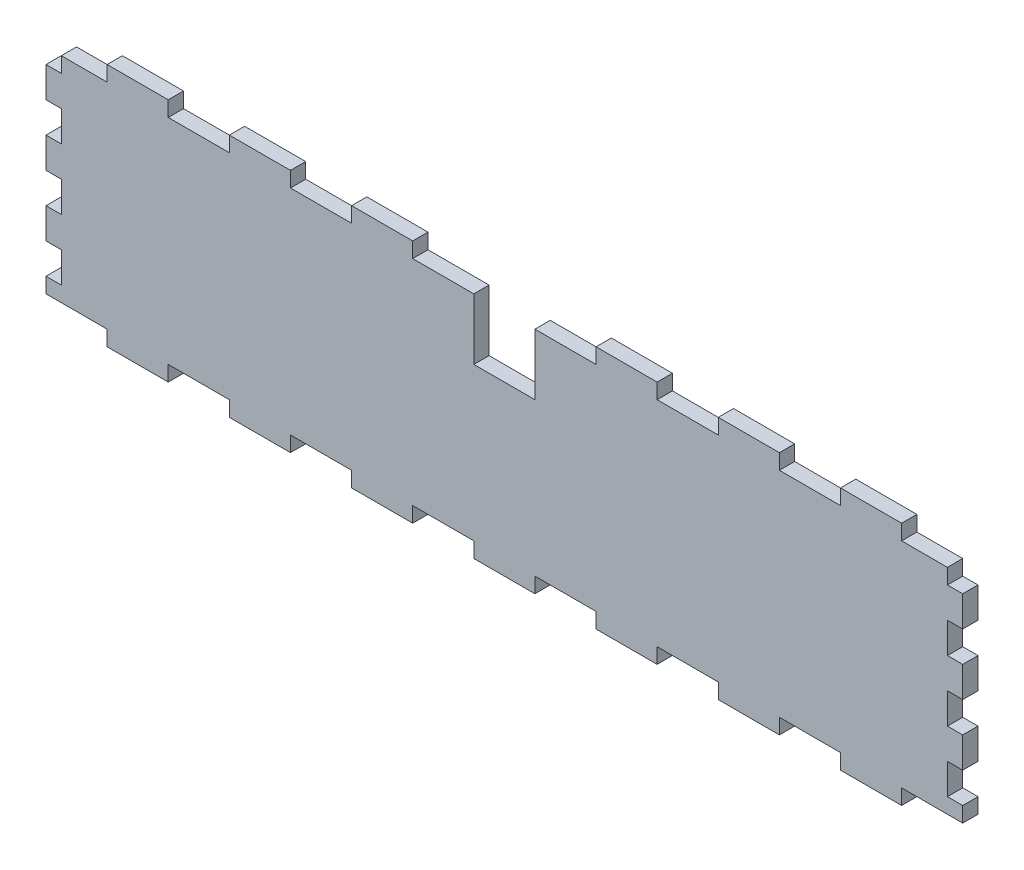
SolidWorks part; units mm, degrees
ref_plane "Front Plane" through (0, 0, 0) normal (0, 0, 1) x (1, 0, 0)
ref_plane "Top Plane" through (0, 0, 0) normal (0, 1, 0) x (1, 0, 0)
ref_plane "Right Plane" through (0, 0, 0) normal (1, 0, 0) x (0, 0, -1)
sketch "Sketch1" plane through (0, 0, 0) normal (0, 0, 1) x (1, 0, 0)
  line L1 (-190.5, -50.8) -> (190.5, -50.8)
  line L2 (-190.5, -50.8) -> (-190.5, 50.8)
  line L3 (-190.5, 50.8) -> (190.5, 50.8)
  line L4 (190.5, -50.8) -> (190.5, 50.8)
  line L5 (-190.5, -50.8) -> (190.5, 50.8) construction
  line L6 (-190.5, 50.8) -> (190.5, -50.8) construction
  point P0 (0, 0)
  dimension "D1" = 381
  dimension "D2" = 101.6
extrude "Boss-Extrude1" add sketch "Sketch1" along normal blind 6.35
sketch "Sketch2" plane through (0, 0, 6.35) normal (0, 0, 1) x (1, 0, 0)
  line L0 (-139.7, 50.8) -> (-139.7, 44.45)
  line L1 (-190.5, 50.8) -> (-165.1, 50.8)
  line L2 (-190.5, 50.8) -> (-190.5, 44.45)
  line L3 (-190.5, 44.45) -> (-165.1, 44.45)
  line L4 (-165.1, 50.8) -> (-165.1, 44.45)
  line L5 (-139.7, 50.8) -> (-114.3, 50.8)
  line L6 (-114.3, 50.8) -> (-114.3, 44.45)
  line L7 (-139.7, 44.45) -> (-114.3, 44.45)
  line L8 (-88.9, 50.8) -> (-88.9, 44.45)
  line L9 (-88.9, 50.8) -> (-63.5, 50.8)
  line L10 (-63.5, 50.8) -> (-63.5, 44.45)
  line L11 (-88.9, 44.45) -> (-63.5, 44.45)
  line L12 (-38.1, 50.8) -> (-38.1, 44.45)
  line L13 (-38.1, 50.8) -> (-12.7, 50.8)
  line L14 (-12.7, 50.8) -> (-12.7, 44.45)
  line L15 (-38.1, 44.45) -> (-12.7, 44.45)
  line L16 (12.7, 50.8) -> (12.7, 44.45)
  line L17 (12.7, 50.8) -> (38.1, 50.8)
  line L18 (38.1, 50.8) -> (38.1, 44.45)
  line L19 (12.7, 44.45) -> (38.1, 44.45)
  line L20 (63.5, 50.8) -> (63.5, 44.45)
  line L21 (63.5, 50.8) -> (88.9, 50.8)
  line L22 (88.9, 50.8) -> (88.9, 44.45)
  line L23 (63.5, 44.45) -> (88.9, 44.45)
  line L24 (114.3, 50.8) -> (114.3, 44.45)
  line L25 (114.3, 50.8) -> (139.7, 50.8)
  line L26 (139.7, 50.8) -> (139.7, 44.45)
  line L27 (114.3, 44.45) -> (139.7, 44.45)
  line L28 (165.1, 50.8) -> (165.1, 44.45)
  line L29 (165.1, 50.8) -> (190.5, 50.8)
  line L30 (190.5, 50.8) -> (190.5, 44.45)
  line L31 (165.1, 44.45) -> (190.5, 44.45)
  line L32 (0, 0) -> (17.1366, 0)
  line L33 (0, 0) -> (0, 20.0911)
  line L34 (165.1, -50.8) -> (190.5, -50.8)
  line L35 (190.5, -50.8) -> (190.5, -44.45)
  line L36 (165.1, -44.45) -> (190.5, -44.45)
  line L37 (165.1, -50.8) -> (165.1, -44.45)
  line L38 (114.3, -50.8) -> (139.7, -50.8)
  line L39 (139.7, -50.8) -> (139.7, -44.45)
  line L40 (114.3, -44.45) -> (139.7, -44.45)
  line L41 (114.3, -50.8) -> (114.3, -44.45)
  line L42 (63.5, -50.8) -> (88.9, -50.8)
  line L43 (88.9, -50.8) -> (88.9, -44.45)
  line L44 (63.5, -44.45) -> (88.9, -44.45)
  line L45 (63.5, -50.8) -> (63.5, -44.45)
  line L46 (12.7, -50.8) -> (38.1, -50.8)
  line L47 (38.1, -50.8) -> (38.1, -44.45)
  line L48 (12.7, -44.45) -> (38.1, -44.45)
  line L49 (12.7, -50.8) -> (12.7, -44.45)
  line L50 (-38.1, -50.8) -> (-12.7, -50.8)
  line L51 (-12.7, -50.8) -> (-12.7, -44.45)
  line L52 (-38.1, -44.45) -> (-12.7, -44.45)
  line L53 (-38.1, -50.8) -> (-38.1, -44.45)
  line L54 (-88.9, -50.8) -> (-63.5, -50.8)
  line L55 (-63.5, -50.8) -> (-63.5, -44.45)
  line L56 (-88.9, -44.45) -> (-63.5, -44.45)
  line L57 (-88.9, -50.8) -> (-88.9, -44.45)
  line L58 (-139.7, -50.8) -> (-114.3, -50.8)
  line L59 (-114.3, -50.8) -> (-114.3, -44.45)
  line L60 (-139.7, -44.45) -> (-114.3, -44.45)
  line L61 (-139.7, -50.8) -> (-139.7, -44.45)
  line L62 (-190.5, -44.45) -> (-165.1, -44.45)
  line L63 (-165.1, -50.8) -> (-165.1, -44.45)
  line L64 (-190.5, -50.8) -> (-165.1, -50.8)
  line L65 (-190.5, -50.8) -> (-190.5, -44.45)
  line L66 (-190.5, 25.4) -> (-190.5, 12.7)
  line L67 (-190.5, 50.8) -> (-184.15, 50.8)
  line L68 (-190.5, 50.8) -> (-190.5, 38.1)
  line L69 (-190.5, 38.1) -> (-184.15, 38.1)
  line L70 (-184.15, 50.8) -> (-184.15, 38.1)
  line L71 (-190.5, 25.4) -> (-184.15, 25.4)
  line L72 (-184.15, 25.4) -> (-184.15, 12.7)
  line L73 (-190.5, 12.7) -> (-184.15, 12.7)
  line L74 (-190.5, 0) -> (-190.5, -12.7)
  line L75 (-190.5, 0) -> (-184.15, 0)
  line L76 (-184.15, 0) -> (-184.15, -12.7)
  line L77 (-190.5, -12.7) -> (-184.15, -12.7)
  line L78 (-190.5, -25.4) -> (-190.5, -38.1)
  line L79 (-190.5, -25.4) -> (-184.15, -25.4)
  line L80 (-184.15, -25.4) -> (-184.15, -38.1)
  line L81 (-190.5, -38.1) -> (-184.15, -38.1)
  line L83 (190.5, -25.4) -> (184.15, -25.4)
  line L84 (184.15, -25.4) -> (184.15, -38.1)
  line L85 (190.5, -38.1) -> (184.15, -38.1)
  line L86 (190.5, -25.4) -> (190.5, -38.1)
  line L87 (190.5, 0) -> (184.15, 0)
  line L88 (184.15, 0) -> (184.15, -12.7)
  line L89 (190.5, -12.7) -> (184.15, -12.7)
  line L90 (190.5, 0) -> (190.5, -12.7)
  line L91 (190.5, 25.4) -> (184.15, 25.4)
  line L92 (184.15, 25.4) -> (184.15, 12.7)
  line L93 (190.5, 12.7) -> (184.15, 12.7)
  line L94 (190.5, 25.4) -> (190.5, 12.7)
  line L95 (190.5, 38.1) -> (184.15, 38.1)
  line L96 (184.15, 50.8) -> (184.15, 38.1)
  line L97 (190.5, 50.8) -> (184.15, 50.8)
  line L98 (190.5, 50.8) -> (190.5, 38.1)
  line M51 (190.5, -50.8) -> (190.5, 50.8)
  line M52 (190.5, 50.8) -> (-190.5, 50.8)
  line M53 (-190.5, 50.8) -> (-190.5, -50.8)
  line M54 (-190.5, -50.8) -> (190.5, -50.8)
  dimension "D1" = 25.4
  dimension "D2" = 6.35
  dimension "D4" = 6.35
  dimension "D5" = 12.7
  dimension "D3" = 8
  dimension "D6" = 4
extrude "Cut-Extrude1" cut sketch "Sketch2" against normal blind 6.35 contours L70 L3 L4 M52 | L70 L1 L3 M53 | L70 L3 L69 M53 | L73 L72 L71 M53 | L77 L76 L75 M53 | L81 L80 L79 M53 | L63 L62 M54 M53 | L61 L59 L60 M54 | L57 L55 L56 M54 | L53 L51 L52 M54 | L49 L47 L48 M54 | L0 L7 L6 M52 | L8 L11 L10 M52 | L12 L15 L14 M52 | L16 L19 L18 M52 | L20 L23 L22 M52 | L45 L43 L44 M54 | L41 L39 L40 M54 | L24 L27 L26 M52 | L96 L29 L28 L31 | L96 L31 M52 M51 | L31 L96 L95 M51 | L93 L91 L92 M51 | L89 L87 L88 M51 | L85 L83 L84 M51 | L37 L36 M54 M51 region at (-127, 47.625, 6.35) region at (-174.625, 47.625, 6.35) region at (-76.2, 47.625, 6.35) region at (-187.325, 47.625, 6.35) region at (-187.325, 41.275, 6.35) region at (-25.4, 47.625, 6.35) region at (25.4, 47.625, 6.35) region at (-187.325, 19.05, 6.35) region at (76.2, 47.625, 6.35) region at (-187.325, -6.35, 6.35) region at (127, 47.625, 6.35) region at (-187.325, -31.75, 6.35) region at (174.625, 47.625, 6.35) region at (-177.8, -47.625, 6.35) region at (187.325, 47.625, 6.35) region at (187.325, 41.275, 6.35) region at (-127, -47.625, 6.35) region at (187.325, 19.05, 6.35) region at (-76.2, -47.625, 6.35) region at (187.325, -6.35, 6.35) region at (-25.4, -47.625, 6.35) region at (187.325, -31.75, 6.35) region at (25.4, -47.625, 6.35) region at (177.8, -47.625, 6.35) region at (76.2, -47.625, 6.35) region at (127, -47.625, 6.35)
sketch "Sketch3" plane through (0, 0, 6.35) normal (0, 0, 1) x (1, 0, 0)
  line L0 (12.7, 50.8) -> (12.7, 44.45) construction
  line L1 (-12.7, 50.8) -> (12.7, 50.8)
  line L2 (-12.7, 50.8) -> (-12.7, 19.05)
  line L3 (-12.7, 19.05) -> (12.7, 19.05)
  line L4 (12.7, 50.8) -> (12.7, 19.05)
  dimension "D1" = 31.75
extrude "Cut-Extrude2" cut sketch "Sketch3" against normal blind 6.35
